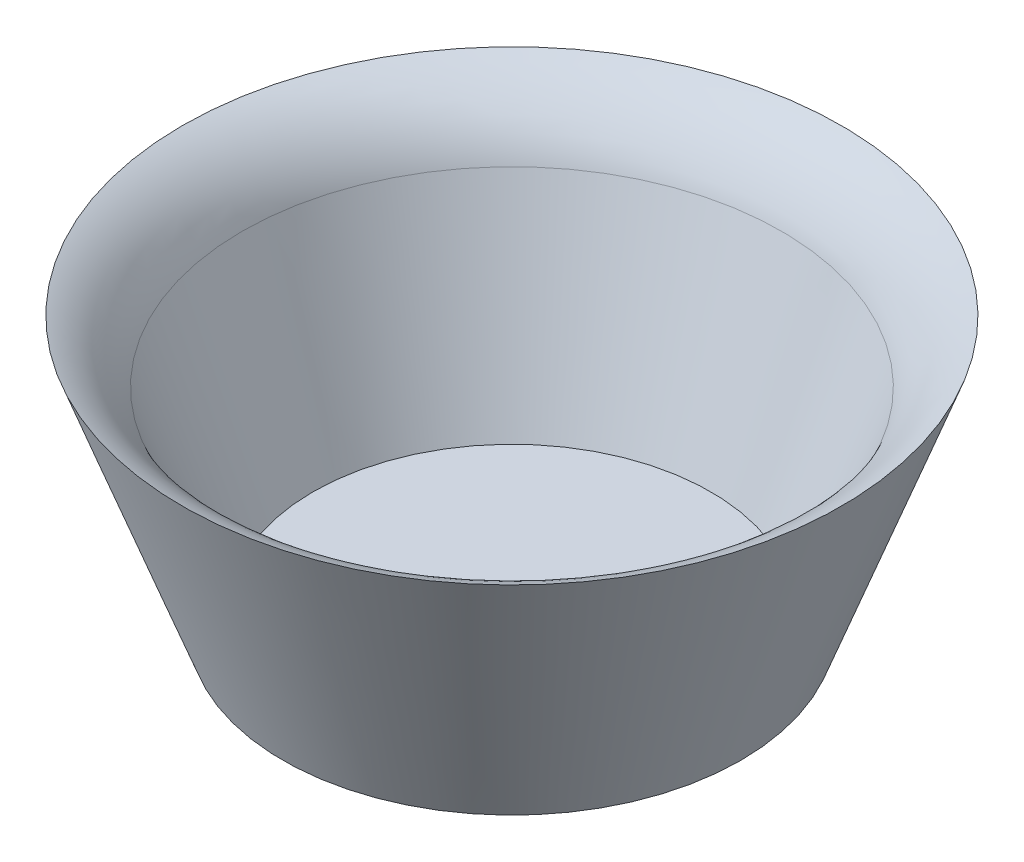
SolidWorks part; units mm, degrees
ref_plane "Front Plane" through (0, 0, 0) normal (0, 0, 1) x (1, 0, 0)
ref_plane "Top Plane" through (0, 0, 0) normal (0, 1, 0) x (1, 0, 0)
ref_plane "Right Plane" through (0, 0, 0) normal (1, 0, 0) x (0, 0, -1)
sketch "Sketch1" plane through (0, 0, 0) normal (0, 0, 1) x (1, 0, 0)
  line L0 (0, 4.9699) -> (0, -29.8303) construction
  line L1 (0, 0) -> (0, -3.5)
  line L2 (0, -3.5) -> (-43, -3.5)
  line L3 (-43, -3.5) -> (-61.8973, 47.3)
  line L4 (-61.8973, 47.3) -> (-54.9621, 47.3)
  line L5 (-54.9621, 47.3) -> (-37.3668, 0)
  line L6 (-37.3668, 0) -> (0, 0)
  dimension "D1" = 43
  dimension "D2" = 50.8
  dimension "D3" = 61.8973
  dimension "D4" = 3.5
  dimension "D5" = 6.5
  dimension "D6" = 110.405
revolve "Revolve1" add sketch "Sketch1" angle 360 about L0
fillet "Fillet1" radius 20 1 edges at (-54.9621, 47.3, 0) tangent propagation no
